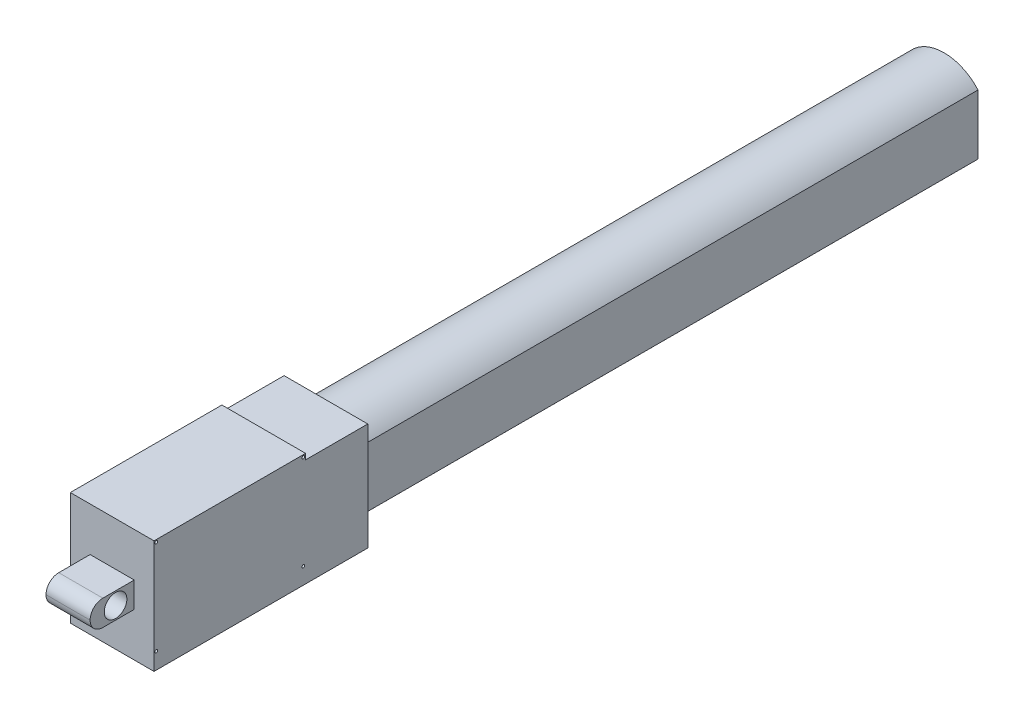
SolidWorks part; units mm, degrees
ref_plane "Front Plane" through (0, 0, 0) normal (0, 0, 1) x (1, 0, 0)
ref_plane "Top Plane" through (0, 0, 0) normal (0, 1, 0) x (1, 0, 0)
ref_plane "Right Plane" through (0, 0, 0) normal (1, 0, 0) x (0, 0, -1)
sketch "Sketch3" plane through (0, 0, 0) normal (0, 0, 1) x (1, 0, 0)
  line L2 (-3.05, -3.3087) -> (-3.05, 3.3087)
  line L4 (3.05, -3.3087) -> (3.05, 3.3087)
  line L6 (-6, -5.2915) -> (-6, 5.2915)
  line L8 (6, -5.2915) -> (6, 5.2915)
  arc A0 (-3.05, -3.3087) -> (3.05, -3.3087) centre (0, 0) ccw
  arc A1 (3.05, 3.3087) -> (-3.05, 3.3087) centre (0, 0) ccw
  arc A2 (-6, -5.2915) -> (6, -5.2915) centre (0, 0) ccw
  arc A3 (6, 5.2915) -> (-6, 5.2915) centre (0, 0) ccw
  point P0 (0, 0)
  point P12 (0, 0)
  dimension "D2" = 4.5
  dimension "D3" = 6.6174
  dimension "D6" = 8
  dimension "D1" = 6.1
  dimension "D4" = 12
  dimension "D5" = 10.583
extrude "Boss-Extrude2" add sketch "Sketch3" along normal blind 109.3
sketch "Sketch4" plane through (0, 0, 109.3) normal (0, 0, 1) x (1, 0, 0)
  line L0 (-3.05, 3.3087) -> (-3.05, -3.3087) construction
  line L1 (-7.4, -9.5) -> (7.4, -9.5)
  line L2 (-7.4, -9.5) -> (-7.4, 9.5)
  line L3 (-7.4, 9.5) -> (7.4, 9.5)
  line L4 (7.4, -9.5) -> (7.4, 9.5)
  line L5 (-7.4, -9.5) -> (7.4, 9.5) construction
  line L6 (-7.4, 9.5) -> (7.4, -9.5) construction
  line L7 (3.05, -3.3087) -> (3.05, 3.3087) construction
  line L8 (-3.05, 3.3087) -> (-3.05, -3.3087)
  line L9 (3.05, -3.3087) -> (3.05, 3.3087)
  arc A0 (3.05, 3.3087) -> (-3.05, 3.3087) centre (0, 0) ccw construction
  arc A1 (-3.05, -3.3087) -> (3.05, -3.3087) centre (0, 0) ccw construction
  arc A2 (-3.05, -3.3087) -> (3.05, -3.3087) centre (0, 0) ccw
  arc A3 (3.05, 3.3087) -> (-3.05, 3.3087) centre (0, 0) ccw
  point P0 (0, 0)
  dimension "D1" = 14.8
  dimension "D2" = 19
extrude "Boss-Extrude3" add sketch "Sketch4" along normal blind 11
sketch "Sketch5" plane through (0, 0, 120.3) normal (0, 0, 1) x (1, 0, 0)
  line L0 (-3.05, 3.3087) -> (-3.05, -3.3087) construction
  line L1 (-7.4, -9.5) -> (7.4, -9.5)
  line L2 (-7.4, -9.5) -> (-7.4, 10.5)
  line L3 (-7.4, 10.5) -> (7.4, 10.5)
  line L4 (7.4, -9.5) -> (7.4, 10.5)
  line L5 (-7.4, -9.5) -> (7.4, 10.5) construction
  line L6 (-7.4, 10.5) -> (7.4, -9.5) construction
  line L7 (3.05, -3.3087) -> (3.05, 3.3087) construction
  line L8 (-3.05, 3.3087) -> (-3.05, -3.3087)
  line L9 (3.05, -3.3087) -> (3.05, 3.3087)
  arc A0 (3.05, 3.3087) -> (-3.05, 3.3087) centre (0, 0) ccw construction
  arc A1 (-3.05, -3.3087) -> (3.05, -3.3087) centre (0, 0) ccw construction
  arc A2 (3.05, 3.3087) -> (-3.05, 3.3087) centre (0, 0) ccw
  arc A3 (-3.05, -3.3087) -> (3.05, -3.3087) centre (0, 0) ccw
  point P0 (0, 0.5)
  point P5 (0, 0)
  dimension "D1" = 14.8
  dimension "D2" = 20
  dimension "D3" = 0.5
extrude "Boss-Extrude4" add sketch "Sketch5" along normal blind 25.4
sketch "Sketch7" plane through (0, 0, 145.7) normal (0, 0, 1) x (1, 0, 0)
  line L0 (-7.4, -9.5) -> (7.4, -9.5) construction
  line L1 (-7.4, 10.5) -> (-7.4, -9.5) construction
  line L2 (7.4, -9.5) -> (7.4, 10.5) construction
  line L3 (7.4, 10.5) -> (-7.4, 10.5) construction
  line L4 (-7.4, -9.5) -> (7.4, -9.5)
  line L5 (-7.4, 10.5) -> (-7.4, -9.5)
  line L6 (7.4, -9.5) -> (7.4, 10.5)
  line L7 (7.4, 10.5) -> (-7.4, 10.5)
extrude "Boss-Extrude5" add sketch "Sketch7" along normal blind 1.4
sketch "Sketch8" plane through (0, 0, 147.1) normal (0, 0, 1) x (1, 0, 0)
  line L0 (7.4, 10.5) -> (-7.4, 10.5) construction
  line L1 (-3.9, -1.75) -> (3.9, -1.75)
  line L2 (-3.9, -1.75) -> (-3.9, 2.75)
  line L3 (-3.9, 2.75) -> (3.9, 2.75)
  line L4 (3.9, -1.75) -> (3.9, 2.75)
  line L5 (-3.9, -1.75) -> (3.9, 2.75) construction
  line L6 (-3.9, 2.75) -> (3.9, -1.75) construction
  line L7 (-7.4, 10.5) -> (-7.4, -9.5) construction
  point P0 (0, 0.5)
  dimension "D1" = 4.5
  dimension "D2" = 7.8
  dimension "D3" = 7.75
  dimension "D4" = 3.5
extrude "Boss-Extrude6" add sketch "Sketch8" along normal blind 7.8
sketch "Sketch9" plane through (-3.9, 0, 0) normal (-1, 0, 0) x (0, 0, 1)
  line L0 (154.9, 2.75) -> (154.9, -1.75) construction
  line L1 (154.9, 2.75) -> (147.1, 2.75) construction
  circle A0 centre (150.4, 0.5) radius 2
  dimension "D1" = 4
  dimension "D2" = 4.5
  dimension "D3" = 2.25
extrude "Cut-Extrude1" cut sketch "Sketch9" against normal through all
fillet "Fillet1" radius 2.25 2 edges at (0, -1.75, 154.9) (0, 2.75, 154.9)
sketch "Sketch10" plane through (-7.4, 0, 0) normal (-1, 0, 0) x (0, 0, 1)
  line L0 (120.3, 10.5) -> (120.3, 9.5) construction
  line L1 (147.1, 10.5) -> (120.3, 10.5) construction
  circle A1 centre (120.7, -6.6) radius 0.25
  circle A3 centre (146.7, -6.6) radius 0.25
  circle A4 centre (120.7, 10.1) radius 0.25
  circle A6 centre (146.7, 10.1) radius 0.25
  point P8 (0, 0)
  point P9 (0, 0)
  point P10 (0, 0)
  point P11 (0, 0)
  dimension "D1" = 0.5
  dimension "D2" = 0.4
  dimension "D3" = 0.4
  dimension "D4" = 26
  dimension "D5" = 16.7
extrude "Cut-Extrude2" cut sketch "Sketch10" against normal through all
sketch "Sketch11" plane through (0, 0, 147.1) normal (0, 0, 1) x (1, 0, 0)
  circle A0 centre (0, 0) radius 12.8456
